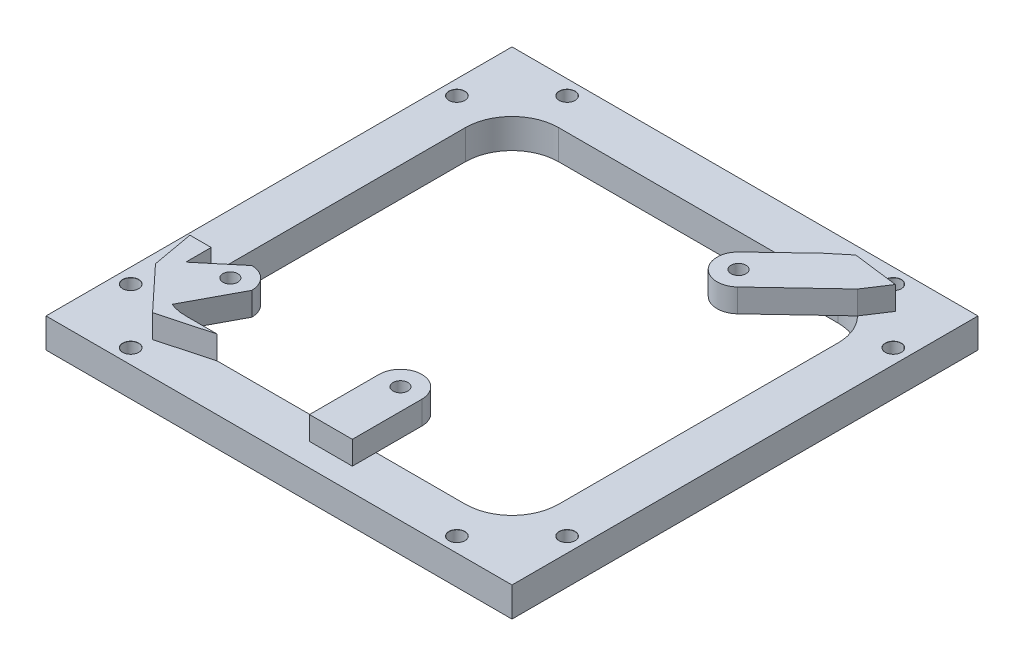
SolidWorks part; units mm, degrees
material "6061 Alloy"
ref_plane "Front Plane" through (0, 0, 0) normal (0, 0, 1) x (1, 0, 0)
ref_plane "Top Plane" through (0, 0, 0) normal (0, 1, 0) x (1, 0, 0)
ref_plane "Right Plane" through (0, 0, 0) normal (1, 0, 0) x (0, 0, -1)
sketch "Sketch1" plane through (0, 0, 0) normal (0, 1, 0) x (1, 0, 0)
  line L1 (-50, -50) -> (50, -50)
  line L2 (-50, -50) -> (-50, 50)
  line L3 (-50, 50) -> (50, 50)
  line L4 (50, -50) -> (50, 50)
  line L5 (-50, -50) -> (50, 50) construction
  line L6 (-50, 50) -> (50, -50) construction
extrude "Boss-Extrude3" add sketch "Sketch1" along normal blind 6.35 contours L1 L4 L3 L2 region at (0, 0, 0)
sketch "Sketch8" plane through (0, 6.35, 0) normal (0, 1, 0) x (1, 0, 0)
  line L0 (-50, -50) -> (-39.5, -50)
  line L1 (-50, -50) -> (50, -50) construction
  line L2 (-39.5, -50) -> (-39.5, -39.5)
  line L3 (50, -50) -> (39.5, -50)
  line L4 (39.5, -50) -> (39.5, -39.5)
  line L5 (50, 50) -> (39.5, 50)
  line L6 (-50, 50) -> (50, 50) construction
  line L7 (39.5, 50) -> (39.5, 39.5)
  line L8 (-50, 50) -> (-39.5, 50)
  line L9 (-50, -50) -> (-50, 50) construction
  line L10 (-39.5, 50) -> (-39.5, 39.5)
sketch "Sketch13" plane through (0, 6.35, 0) normal (0, 1, 0) x (1, 0, 0)
  line L1 (-50, -50) -> (-35, -50)
  line L2 (-50, -50) -> (50, -50) construction
  line L3 (-35, -50) -> (-35, -46.825)
  line L4 (-50, -50) -> (-50, -35)
  line L5 (-50, -50) -> (-50, 50) construction
  line L6 (-50, -35) -> (-46.825, -35)
  line L7 (-50, 50) -> (-35, 50)
  line L8 (-50, 50) -> (50, 50) construction
  line L9 (-35, 50) -> (-35, 46.825)
  line L10 (-50, 50) -> (-50, 35)
  line L11 (-50, 35) -> (-46.825, 35)
  line L13 (50, 50) -> (35, 50)
  line L14 (35, 50) -> (35, 46.825)
  line L15 (50, 50) -> (50, 35)
  line L16 (50, -50) -> (50, 50) construction
  line L17 (50, 35) -> (46.825, 35)
  line L18 (50, -50) -> (50, -35)
  line L19 (50, -35) -> (46.825, -35)
  line L20 (50, -50) -> (35, -50)
  line L21 (35, -50) -> (35, -46.825)
hole_wizard "M3 Clearance Hole1" positions "Sketch17" profile "Sketch18" hole size "M3" standard "ANSI Metric" end condition through all
sketch "Sketch17" plane through (0, 6.35, 0) normal (0, 1, 0) x (1, 0, 0)
  point P0 (-46.825, 35)
  point P3 (-35, 46.825)
  point P6 (35, 46.825)
  point P9 (46.825, 35)
  point P12 (46.825, -35)
  point P15 (35, -46.825)
  point P18 (-35, -46.825)
  point P21 (-46.825, -35)
sketch "Sketch18" plane through (-46.825, 6.35, -35) normal (1, 0, 0) x (0, 0, 1)
  line L0 (0, 0) -> (0, 6.35)
  line L1 (0, 6.35) -> (1.7, 6.35)
  line L2 (1.7, 6.35) -> (1.7, 0.025)
  line L3 (1.7, 0.025) -> (1.725, 0)
  line L5 (1.725, 0) -> (0, 0)
  line L6 (-1.7, 0.025) -> (-1.725, 0) construction
  line L11 (0, -6.35) -> (0, 107.95) construction
  dimension "Thru Hole Dia." = 3.4
  dimension "Thru Hole Depth" = 6.35
  dimension "Near C'Sink Dia." = 3.45
  dimension "Near C'Sink Angle" = 90
sketch "Sketch19" plane through (0, 6.35, 0) normal (0, 1, 0) x (1, 0, 0)
  line L1 (-30, -40) -> (30, -40)
  line L2 (-40, -30) -> (-40, 30)
  line L3 (-30, 40) -> (30, 40)
  line L4 (40, -30) -> (40, 30)
  line L5 (-40, -40) -> (40, 40) construction
  line L6 (-40, 40) -> (40, -40) construction
  arc A0 (-30, -40) -> (-40, -30) centre (-30, -30) cw
  arc A1 (40, -30) -> (30, -40) centre (30, -30) cw
  arc A2 (30, 40) -> (40, 30) centre (30, 30) cw
  arc A3 (-30, 40) -> (-40, 30) centre (-30, 30) ccw
  point P0 (0, 0)
  dimension "D1" = 10
extrude "Cut-Extrude1" cut sketch "Sketch19" against normal blind 10
sketch "Sketch20" plane through (0, 6.35, -6.35) normal (0, -1, 0) x (1, 0, 0)
  line L0 (-32.2781, 29.9112) -> (-40, 36.35)
  line L1 (-27.6781, 34.5112) -> (-33.6259, 45.6695)
  line L2 (6.2004, 36.4882) -> (20.6711, -21.587) construction
  line L3 (-32.2781, 34.5112) -> (6.2004, 36.4882) construction
  line L4 (20.6711, -21.587) -> (-32.2781, 34.5112) construction
  line L5 (1.6004, 36.4882) -> (1.6004, 46.35)
  line L6 (-30, 46.35) -> (30, 46.35) construction
  line L7 (10.8004, 36.4882) -> (10.8004, 46.35)
  line L8 (23.8259, -18.2393) -> (37.0711, -30.7211)
  line L9 (17.5038, -24.9228) -> (26.6951, -33.65)
  line L10 (30, -33.65) -> (-30, -33.65) construction
  line L11 (-40, 36.35) -> (-40, 30.905)
  line L12 (-40, -23.65) -> (-40, 36.35) construction
  line L13 (-40, 30.905) -> (-44.5625, 30.905)
  line L14 (-44.5625, 30.905) -> (-42.9492, 39.9051)
  line L15 (-42.9492, 39.9051) -> (-34.1675, 49.3172)
  line L16 (-34.1675, 49.3172) -> (-23.285, 46.35)
  line L17 (-23.285, 46.35) -> (-33.6259, 45.6695)
  line L18 (1.6004, 46.35) -> (1.6004, 51.4058)
  line L19 (1.6004, 51.4058) -> (10.8004, 51.4058)
  line L20 (10.8004, 51.4058) -> (10.8004, 46.35)
  line L21 (26.6951, -33.65) -> (30.5647, -36.8517)
  line L22 (30.5647, -36.8517) -> (40.2934, -35.6218)
  line L23 (40.2934, -35.6218) -> (37.0711, -30.7211)
  circle A0 centre (-32.2781, 34.5112) radius 1.6
  arc A1 (23.8259, -18.2393) -> (17.5038, -24.9228) centre (20.6711, -21.587) ccw
  arc A2 (1.6004, 36.4882) -> (10.8004, 36.4882) centre (6.2004, 36.4882) ccw
  circle A3 centre (20.6711, -21.587) radius 1.6
  circle A4 centre (6.2004, 36.4882) radius 1.6
  arc A5 (-27.6841, 34.7472) -> (-32.2781, 29.9112) centre (-32.2781, 34.5112) cw
  arc A7 (-30, 46.35) -> (-40, 36.35) centre (-30, 36.35) ccw construction
  circle A8 centre (-32.2781, 34.5112) radius 4.6 construction
  circle A9 centre (6.2004, 36.4882) radius 4.6 construction
  arc A10 (30, -33.65) -> (40, -23.65) centre (30, -23.65) ccw construction
  circle A11 centre (20.6711, -21.587) radius 4.6 construction
  arc M7 (-30, 46.35) -> (-40, 36.35) centre (-30, 36.35) ccw
  line M8 (-40, 36.35) -> (-40, -23.65)
  line M10 (-30, -33.65) -> (30, -33.65)
  arc M11 (30, -33.65) -> (40, -23.65) centre (30, -23.65) ccw
  line M14 (30, 46.35) -> (-30, 46.35)
  dimension "D1" = 77.1403
  dimension "D2" = 58.0752
  dimension "D3" = 38.4785
  dimension "D4" = 49.595
  dimension "D5" = 3
extrude "Boss-Extrude4" add sketch "Sketch20" against normal blind 5 contours A1 L8 L9 A3 M11 M10 | A2 L5 L7 A4 M14 | L1 A5 L0 A0 M7 | L15 L16 L13 L14 M14 M7 M8 | L19 L20 L18 M14 | L23 L22 L21 M10 M11 region at (6.2004, 6.35, 42.5279) region at (6.2004, 6.35, 33.4376) region at (-33.9608, 6.35, 31.1479) region at (-40.2814, 6.35, 27.2775) region at (25.7143, 6.35, -32.3978) region at (34.2218, 6.35, -40.7802)
